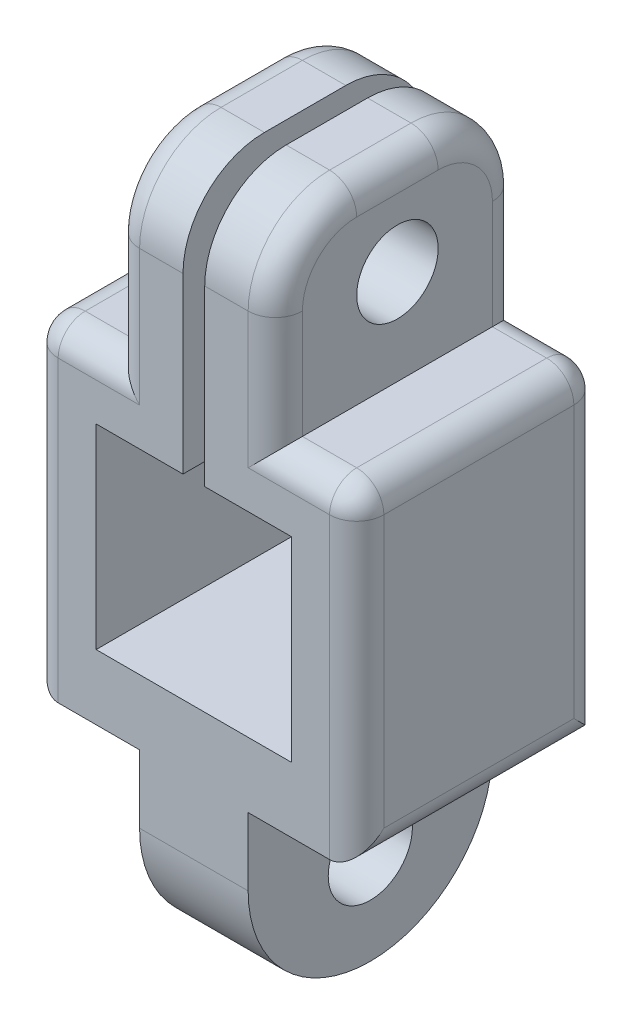
SolidWorks part; units mm, degrees
ref_plane "前视基准面" through (0, 0, 0) normal (0, 0, 1) x (1, 0, 0)
ref_plane "上视基准面" through (0, 0, 0) normal (0, 1, 0) x (1, 0, 0)
ref_plane "右视基准面" through (0, 0, 0) normal (1, 0, 0) x (0, 0, -1)
sketch "草图1" plane through (0, 0, 0) normal (0, 0, 1) x (1, 0, 0)
  line L0 (-1.5, -6) -> (-1.5, -13)
  line L1 (-3.5, 3.5) -> (3.5, 3.5)
  line L2 (-3.5, 3.5) -> (-3.5, -3.5)
  line L3 (-3.5, -3.5) -> (3.5, -3.5)
  line L4 (3.5, 3.5) -> (3.5, -3.5)
  line L5 (-3.5, 3.5) -> (3.5, -3.5) construction
  line L6 (-3.5, -3.5) -> (3.5, 3.5) construction
  line L7 (-6, 6) -> (6, 6)
  line L8 (-6, 6) -> (-6, -6)
  line L9 (-6, -6) -> (6, -6)
  line L10 (6, 6) -> (6, -6)
  line L11 (-6, 6) -> (6, -6) construction
  line L12 (-6, -6) -> (6, 6) construction
  line L13 (-1.5, -13) -> (3.5, -13)
  line L14 (3.5, -13) -> (3.5, -6)
  line L15 (0, 0) -> (0, 9.9638) construction
  line L17 (0, 6) -> (3, 6)
  line L18 (0, 6) -> (0, 13)
  line L19 (0, 13) -> (3, 13)
  line L20 (3, 6) -> (3, 13)
  line L21 (0, 6) -> (-3, 6)
  line L22 (0, 6) -> (0, 13)
  line L23 (0, 13) -> (-3, 13)
  line L24 (-3, 6) -> (-3, 13)
  point P0 (0, 0)
  point P6 (0, 0)
  dimension "D1" = 7
  dimension "D2" = 7
  dimension "D3" = 12
  dimension "D4" = 12
  dimension "D5" = 2
  dimension "D6" = 7
  dimension "D7" = 5
  dimension "D8" = 7
  dimension "D9" = 3
  dimension "D10" = 3
  dimension "D11" = 7
extrude "凸台-拉伸1" add sketch "草图1" along normal blind 9 contours L24 L7 L18 L23 | L7 L20 L19 L18 | L10 L7 L8 L9 L1 L4 L3 L2 | L13 L14 L9 L0 region at (1, -9.5, 0) region at (-3.75, -5.8303, 0) region at (-1.5, 9.5, 0) region at (1.5, 9.5, 0)
sketch "草图2" plane through (0, 0, 9) normal (0, 0, 1) x (1, 0, 0)
  line L0 (0, 16.6392) -> (0, -1.0512) construction
  line L1 (3, 13) -> (-3, 13) construction
  line L2 (0, 13) -> (0.4, 13)
  line L4 (0, 3.5) -> (0.4, 3.5)
  line L5 (0.4, 13) -> (0.4, 3.5)
  line L6 (-3.5, 3.5) -> (3.5, 3.5) construction
  line L8 (0, 13) -> (-0.4, 13)
  line L10 (0, 3.5) -> (-0.4, 3.5)
  line L11 (-0.4, 13) -> (-0.4, 3.5)
  dimension "D1" = 0.4
  dimension "D2" = 0.4
extrude "切除-拉伸1" cut sketch "草图2" against normal through all contours L2 L5 L4 L10 L11 L8
fillet "圆角2" radius 3 4 edges at (1.7, 13, 0) (-1.7, 13, 0) (-1.7, 13, 9) (1.7, 13, 9)
sketch "草图4" plane through (3, 0, 0) normal (1, 0, 0) x (0, 0, -1)
  line L0 (-4.5, 6) -> (-4.5, 9.5) construction
  line L1 (-9, 6) -> (0, 6) construction
  circle A0 centre (-4.5, 9.5) radius 1.5
  dimension "D2" = 3
  dimension "D1" = 3.5
extrude "切除-拉伸3" cut sketch "草图4" against normal through all
fillet "圆角3" radius 1 11 edges at (3, 8, 0) (3, 12.1213, 0.8787) (3, 13, 4.5) (3, 12.1213, 8.1213) (3, 8, 9) (6, -6, 4.5) (6, 0, 0) (6, 0, 9) (6, 6, 4.5) (4.5, 6, 0) (4.5, 6, 9)
fillet "圆角4" radius 1 10 edges at (-3, 8, 0) (-3, 12.1213, 0.8787) (-3, 13, 4.5) (-3, 12.1213, 8.1213) (-3, 8, 9) (-6, -6, 4.5) (-6, 0, 0) (-4.5, 6, 0) (-4.5, 6, 9) (-6, 0, 9)
fillet "圆角5" radius 1 3 edges at (-5.7071, 5.7071, 8.7071) (-5.7071, 5.7071, 0.2929) (-6, 6, 4.5)
sketch "草图5" plane through (0, 0, 9) normal (0, 0, 1) x (1, 0, 0)
  line L1 (-1.5, -6) -> (3.5, -6)
  line L2 (-1.5, -6) -> (-1.5, -13)
  line L3 (-1.5, -13) -> (3.5, -13)
  line L4 (3.5, -6) -> (3.5, -13)
extrude "切除-拉伸4" cut sketch "草图5" against normal blind 9
sketch "草图6" plane through (0, -6, 0) normal (0, -1, 0) x (1, 0, 0)
  line L0 (0, 10.5627) -> (0, -2.0403) construction
  line L1 (-5, 9) -> (5, 9) construction
  line L2 (0, 9) -> (-2, 9)
  line L4 (0, 0) -> (-2, 0)
  line L5 (-2, 9) -> (-2, 0)
  line L6 (-5, 0) -> (5, 0) construction
  line L8 (0, 9) -> (2, 9)
  line L10 (0, 0) -> (2, 0)
  line L11 (2, 9) -> (2, 0)
  dimension "D1" = 2
  dimension "D2" = 2
extrude "凸台-拉伸2" add sketch "草图6" along normal blind 7
fillet "圆角6" radius 4.5 2 edges at (0, -13, 0) (0, -13, 9)
sketch "草图7" plane through (-2, 0, 0) normal (-1, 0, 0) x (0, 0, 1)
  line L0 (4.5, -13) -> (4.5, -9.5) construction
  circle A0 centre (4.5, -9.5) radius 1.55
  dimension "D2" = 3.1
  dimension "D1" = 3.5
extrude "切除-拉伸5" cut sketch "草图7" against normal blind 4
sketch "草图8" plane through (0, 0, 9) normal (0, 0, 1) x (1, 0, 0)
  line L1 (3.5, 3.5) -> (3.6, 3.5)
  line L2 (3.5, 3.5) -> (3.5, -3.6)
  line L3 (3.5, -3.6) -> (3.6, -3.6)
  line L4 (3.6, 3.5) -> (3.6, -3.6)
  line L5 (3.5, -3.5) -> (-3.6, -3.5)
  line L6 (3.5, -3.5) -> (3.5, -3.6)
  line L7 (3.5, -3.6) -> (-3.6, -3.6)
  line L8 (-3.6, -3.5) -> (-3.6, -3.6)
  line L9 (-3.5, -3.5) -> (-3.6, -3.5)
  line L10 (-3.5, -3.5) -> (-3.5, 3.6)
  line L11 (-3.5, 3.6) -> (-3.6, 3.6)
  line L12 (-3.6, -3.5) -> (-3.6, 3.6)
  line L13 (-3.5, 3.5) -> (3.6, 3.5)
  line L14 (-3.5, 3.5) -> (-3.5, 3.6)
  line L15 (-3.5, 3.6) -> (3.6, 3.6)
  line L16 (3.6, 3.5) -> (3.6, 3.6)
  line M17 (0.4, 10) -> (0.4, 3.5)
  line M18 (0.4, 3.5) -> (3.5, 3.5)
  line M19 (3.5, 3.5) -> (3.5, -3.5)
  line M20 (3.5, -3.5) -> (-3.5, -3.5)
  line M21 (-3.5, -3.5) -> (-3.5, 3.5)
  line M22 (-3.5, 3.5) -> (-0.4, 3.5)
  line M23 (-0.4, 3.5) -> (-0.4, 10)
  dimension "D1" = 7.1
  dimension "D2" = 0.1
  dimension "D3" = 7.1
  dimension "D4" = 0.1
  dimension "D5" = 0.1
  dimension "D6" = 7.1
  dimension "D7" = 0.1
  dimension "D8" = 7.1
extrude "切除-拉伸6" cut sketch "草图8" against normal through all contours L15 L10 M22 M23 | L1 L16 L15 M17 M18 | L4 L1 L2 L3 M19 | L12 L5 L10 L11 M21 | L5 L8 L7 L2 M20 region at (2, 3.55, 9) region at (3.55, -0.05, 9) region at (-0.05, -3.55, 9) region at (-3.55, 0.05, 9) region at (-1.95, 3.55, 9)
